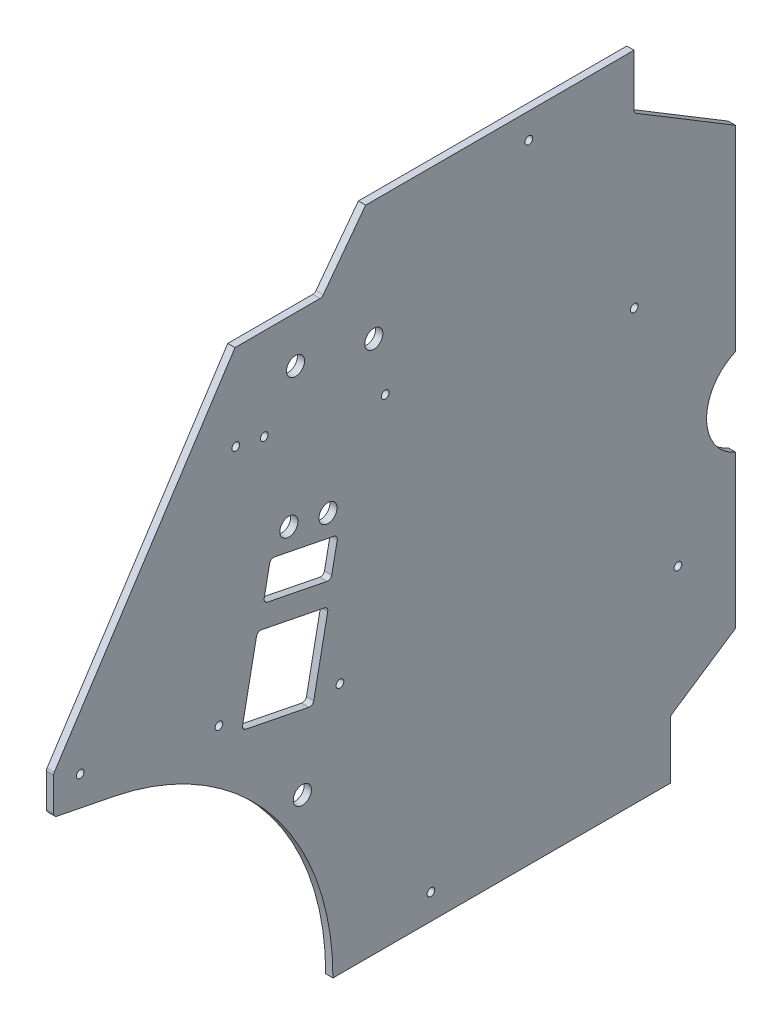
SolidWorks part; units mm, degrees
note: The reader was unsure of these and kept them because the rebuilt part matched: thickness of "Base-Flange1", "Sheet-Metal1", "Sheet-Metal3", "Sheet-Metal4", "Sheet-Metal5", "Sheet-Metal6", "Sheet-Metal7", "Sheet-Metal8", "Sheet-Metal9", "Sheet-Metal10", "Sheet-Metal11", "Sheet-Metal12", "Sheet-Metal13".
material "PE High Density"
ref_plane "Front Plane" through (0, 0, 0) normal (0, 0, 1) x (1, 0, 0)
ref_plane "Top Plane" through (0, 0, 0) normal (0, 1, 0) x (1, 0, 0)
ref_plane "Right Plane" through (0, 0, 0) normal (1, 0, 0) x (0, 0, -1)
sketch "Sketch1" plane through (0, 0, 0) normal (1, 0, 0) x (0, 0, -1)
  line L0 (0, 38.1) -> (-1054.1, 247.7735) construction
  line L1 (-812.8, 571.5) -> (-812.8, 527.05) construction
  line L2 (-381, 0) -> (-425.45, 0) construction
  line L3 (-381, 0) -> (-381, 527.05) construction
  line L4 (-381, 527.05) -> (-425.45, 527.05) construction
  line L5 (-425.45, 0) -> (-425.45, 527.05) construction
  line L6 (0, 571.5) -> (-857.25, 571.5) construction
  line L7 (0, 571.5) -> (0, 527.05) construction
  line L8 (0, 527.05) -> (-857.25, 527.05) construction
  line L9 (-857.25, 571.5) -> (-857.25, 527.05) construction
  line L10 (-1054.1, 247.7735) -> (-876.3, 520.7)
  line L12 (-438.15, 125.2535) -> (-438.15, 571.5)
  line L13 (-438.15, 571.5) -> (-800.1, 571.5)
  line L14 (-800.1, 571.5) -> (-800.1, 520.7)
  line L15 (-800.1, 520.7) -> (-876.3, 520.7)
  line L16 (-74.137, 298.8741) -> (-1150.5711, 512.9902) construction
  line L18 (-790.575, 0) -> (-438.15, 0)
  line L19 (-438.15, 0) -> (-438.15, 125.2535)
  line L20 (-1054.1, 247.7735) -> (-982.1765, 233.467)
  arc A0 (-982.1765, 233.467) -> (-790.575, 0) centre (-1028.6159, 0) cw
  dimension "D1" = 38.1
  dimension "D2" = 381
  dimension "D3" = 44.45
  dimension "D4" = 11.25
  dimension "D5" = 628.65
  dimension "D6" = 571.5
  dimension "D7" = 44.45
  dimension "D8" = 812.8
  dimension "D9" = 12.7
  dimension "D10" = 241.3
  dimension "D11" = 12.7
  dimension "D12" = 12.7
  dimension "D13" = 33.083
  dimension "D14" = 352.425
  dimension "D15" = 76.2
base flange "Base-Flange1" sketch "Sketch1" thickness 6.35 reverse thickness direction no parameters "D1"=3
hole_wizard "1/4 Clearance Hole1" positions "Sketch9" profile "Sketch10" hole size "1/4" standard "ANSI Inch" end condition through all
sketch "Sketch9" plane through (0, 0, 0) normal (1, 0, 0) x (0, 0, -1)
  line L0 (-1049.1447, 272.6855) -> (-451.258, 153.7584) construction
  line L1 (-1054.1, 247.7735) -> (-456.2133, 128.8465) construction
  line L2 (0, 38.1) -> (-1054.1, 247.7735) construction
  line L3 (-1054.1, 247.7735) -> (-1049.1447, 272.6855) construction
  line L4 (-750.2014, 213.2219) -> (-755.1566, 188.31) construction
  line L5 (-438.15, 384.2296) -> (-920.4692, 480.1689) construction
  line L8 (-438.15, 0) -> (-438.15, 571.5) construction
  line L9 (-477.0095, 366.0616) -> (-925.4245, 455.2569) construction
  line L10 (-925.4245, 455.2569) -> (-920.4692, 480.1689) construction
  line L11 (-701.217, 410.6593) -> (-696.2617, 435.5712) construction
  line L12 (-890.331, 241.0955) -> (-784.4553, 220.0355) construction
  line L13 (-890.331, 241.0955) -> (-850.6887, 440.391) construction
  line L14 (-784.4553, 220.0355) -> (-744.8129, 419.331) construction
  line L15 (-850.6887, 440.391) -> (-744.8129, 419.331) construction
  line L16 (-1054.1, 370.7872) -> (-456.2133, 251.8601) construction
  line L17 (-800.1, 527.05) -> (-438.15, 527.05) construction
  line L18 (-800.1, 571.5) -> (-800.1, 520.7) construction
  line L19 (-438.15, 0) -> (-438.15, 571.5) construction
  line L20 (-438.15, 571.5) -> (-800.1, 571.5) construction
  line L21 (-619.125, 527.05) -> (-619.125, 571.5) construction
  line L22 (-438.15, 44.45) -> (-794.762, 44.45) construction
  line L23 (-790.575, 0) -> (-438.15, 0) construction
  line L24 (-704.85, 44.45) -> (-704.85, 0) construction
  circle A0 centre (-1054.1, 370.7872) radius 120.65 construction
  arc A1 (-790.575, 0) -> (-982.1765, 233.467) centre (-1028.6159, 0) ccw construction
  point P18 (-1011.7768, 265.2525)
  point P39 (-488.6259, 161.1914)
  point P60 (-875.6006, 445.3463)
  point P71 (-526.8334, 375.9722)
  point P123 (-850.6887, 440.391)
  point P126 (-744.8129, 419.331)
  point P129 (-890.331, 241.0955)
  point P132 (-784.4553, 220.0355)
  point P139 (-619.125, 549.275)
  point P166 (-704.85, 22.225)
  dimension "D12" = 241.3
  dimension "D1" = 25.4
  dimension "D2" = 38.1
  dimension "D4" = 609.6
  dimension "D5" = 254
  dimension "D6" = 25.4
  dimension "D7" = 50.8
  dimension "D8" = 44.45
  dimension "D9" = 457.2
  dimension "D10" = 107.95
  dimension "D11" = 203.2
  dimension "D13" = 76.2
  dimension "D14" = 85.725
  dimension "D16" = 44.45
  dimension "D17" = 266.7
sketch "Sketch10" plane through (0, 22.225, 704.85) normal (0, 1, 0) x (0, 0, -1)
  line L0 (0, 0) -> (0, 6.35)
  line L1 (0, 6.35) -> (3.3782, 6.35)
  line L2 (3.3782, 6.35) -> (3.3782, 0)
  line L5 (3.3782, 0) -> (0, 0)
  line L11 (0, -6.35) -> (0, 107.95) construction
  dimension "Thru Hole Dia." = 6.7564
  dimension "Thru Hole Depth" = 6.35
sketch "Sketch11" plane through (0, 0, 0) normal (1, 0, 0) x (0, 0, -1)
  line L0 (-845.2967, 345.4396) -> (-786.1308, 333.6708)
  line L1 (-845.2967, 345.4396) -> (-851.4908, 314.2997)
  line L2 (-786.1308, 333.6708) -> (-792.3249, 302.5309)
  line L3 (-851.4908, 314.2997) -> (-792.3249, 302.5309)
  line L4 (-1054.1, 370.7872) -> (-456.2133, 251.8601) construction
  line L5 (-871.7487, 334.5153) -> (-765.8729, 313.4553) construction
  line L6 (-890.331, 241.0955) -> (-850.6887, 440.391) construction
  line L7 (-784.4553, 220.0355) -> (-744.8129, 419.331) construction
  line L8 (-848.3937, 329.8697) -> (-789.2279, 318.1009) construction
  point P0 (-848.3937, 329.8697)
  point P3 (-818.8108, 323.9853)
  dimension "D1" = 31.75
  dimension "D2" = 60.325
extrude "Cut-Extrude1" cut sketch "Sketch11" against normal through all normal cut yes
hole_wizard "27/32 (0.84375) Diameter Hole1" positions "Sketch12" profile "Sketch13" hole size "27/32" standard "ANSI Inch" end condition through all
sketch "Sketch12" plane through (0, 0, 0) normal (1, 0, 0) x (0, 0, -1)
  line L0 (-837.3932, 230.5655) -> (-797.7508, 429.861) construction
  line L1 (-890.331, 241.0955) -> (-784.4553, 220.0355) construction
  line L2 (-850.6887, 440.391) -> (-744.8129, 419.331) construction
  line L3 (-822.4528, 234.068) -> (-849.8559, 239.5189) construction
  line L4 (-1049.1447, 272.6855) -> (-451.258, 153.7584) construction
  line L5 (-1054.1, 370.7872) -> (-456.2133, 251.8601) construction
  point P0 (-849.8559, 239.5189)
  point P2 (-822.4528, 234.068)
  dimension "D1" = 13.97
  dimension "D2" = 88.9
sketch "Sketch13" plane through (0, 239.5189, 849.8559) normal (0, 1, 0) x (0, 0, -1)
  line L0 (0, 0) -> (0, 6.35)
  line L1 (0, 6.35) -> (10.7156, 6.35)
  line L2 (10.7156, 6.35) -> (10.7156, 0)
  line L5 (10.7156, 0) -> (0, 0)
  line L11 (0, -6.35) -> (0, 107.95) construction
  dimension "Thru Hole Dia." = 21.4312
  dimension "Thru Hole Depth" = 6.35
sketch "Sketch14" plane through (0, 0, 0) normal (1, 0, 0) x (0, 0, -1)
  line L0 (-864.1972, 258.5575) -> (-801.9173, 246.1693) construction
  line L1 (-864.1972, 258.5575) -> (-870.3913, 227.4176)
  line L2 (-801.9173, 246.1693) -> (-808.1115, 215.0294)
  line L3 (-870.3913, 227.4176) -> (-808.1115, 215.0294)
  line L4 (-864.1972, 258.5575) -> (-856.7643, 295.9255)
  line L5 (-851.4908, 314.2997) -> (-792.3249, 302.5309) construction
  line L6 (-849.8559, 239.5189) -> (-822.4528, 234.068) construction
  line L7 (-836.1543, 236.7935) -> (-833.0573, 252.3634) construction
  line L8 (-856.7643, 295.9255) -> (-794.4844, 283.5372)
  line L9 (-794.4844, 283.5372) -> (-801.9173, 246.1693)
  circle A0 centre (-849.8559, 239.5189) radius 10.7156 construction
  circle A1 centre (-849.8559, 239.5189) radius 10.7156 construction
  dimension "D1" = 15.875
  dimension "D2" = 31.75
  dimension "D3" = 63.5
  dimension "D4" = 19.05
  dimension "D5" = 38.1
extrude "Cut-Extrude2" cut sketch "Sketch14" against normal through all normal cut yes
sketch "Sketch15" plane through (0, 0, 0) normal (1, 0, 0) x (0, 0, -1)
  line L0 (-438.15, 0) -> (-438.15, 571.5) construction
  line L1 (-438.15, 571.5) -> (-476.25, 571.5)
  line L2 (-438.15, 571.5) -> (-438.15, 501.878)
  line L3 (-438.15, 501.878) -> (-476.25, 523.875)
  line L4 (-476.25, 571.5) -> (-476.25, 523.875)
  line L5 (-438.15, 0) -> (-495.3, 0)
  line L6 (-438.15, 0) -> (-438.15, 88.9)
  line L7 (-438.15, 88.9) -> (-495.3, 50.8)
  line L8 (-495.3, 0) -> (-495.3, 50.8)
  line L9 (-438.15, 571.5) -> (-800.1, 571.5) construction
  dimension "D1" = 60
  dimension "D2" = 38.1
  dimension "D3" = 47.625
  dimension "D4" = 57.15
  dimension "D5" = 50.8
  dimension "D6" = 88.9
extrude "Cut-Extrude3" cut sketch "Sketch15" against normal through all normal cut yes
sketch "Sketch16" plane through (-6.35, 0, 0) normal (-1, 0, 0) x (0, 0, 1)
  line L0 (795.5084, 300.5226) -> (797.4905, 290.5578) construction
  line L1 (851.4908, 314.2997) -> (792.3249, 302.5309) construction
  line L4 (815.7138, 339.5552) -> (821.9079, 308.4153) construction
  line L5 (786.1308, 333.6708) -> (845.2967, 345.4396) construction
  line L6 (798.7398, 303.8069) -> (801.2273, 291.3011)
  line L9 (793.7537, 289.8145) -> (791.7716, 299.7793)
  line L10 (791.7716, 299.7793) -> (791.1522, 302.8933)
  line L12 (791.1522, 302.8933) -> (791.7055, 305.6449)
  line L13 (792.3249, 302.5309) -> (786.1308, 333.6708) construction
  line L14 (791.7055, 305.6449) -> (792.3249, 302.5309)
  line L15 (792.3249, 302.5309) -> (798.7398, 303.8069)
  line L16 (851.4908, 314.2997) -> (845.076, 313.0237)
  line L17 (850.8714, 317.4137) -> (851.4908, 314.2997)
  line L18 (852.4356, 315.0833) -> (850.8714, 317.4137)
  line L19 (853.055, 311.9693) -> (852.4356, 315.0833)
  line L20 (855.0371, 302.0045) -> (853.055, 311.9693)
  line L21 (845.076, 313.0237) -> (847.5635, 300.5179)
  circle A4 centre (795.5084, 300.5226) radius 3.81 construction
  circle A5 centre (797.4905, 290.5578) radius 3.81 construction
  circle A6 centre (851.3003, 301.2612) radius 3.81 construction
  circle A7 centre (849.3182, 311.226) radius 3.81 construction
  arc A8 (793.7537, 289.8145) -> (801.2273, 291.3011) centre (797.4905, 290.5578) ccw
  arc A9 (855.0371, 302.0045) -> (847.5635, 300.5179) centre (851.3003, 301.2612) cw
  dimension "D4" = 7.62
  dimension "D1" = 2.5908
  dimension "D2" = 10.16
  dimension "D3" = 54.864
  dimension "D5" = 3.175
  dimension "D6" = 3.175
extrude "Cut-Extrude4" [suppressed] cut sketch "Sketch16" against normal through all
fillet "Fillet1" [suppressed] radius 3.556
sketch "Sketch17" plane through (-6.35, 0, 0) normal (-1, 0, 0) x (0, 0, 1)
  line L0 (1035.05, 277.0156) -> (1035.05, 243.9842)
  line L1 (876.3, 520.7) -> (1054.1, 247.7735) construction
  line L2 (1054.1, 247.7735) -> (982.1765, 233.467) construction
  line L3 (1035.05, 243.9842) -> (1054.1, 247.7735)
  line L4 (1054.1, 247.7735) -> (1035.05, 277.0156)
  dimension "D1" = 19.05
extrude "Cut-Extrude5" cut sketch "Sketch17" against normal through all normal cut yes
sketch "Sketch18" plane through (-6.35, 0, 0) normal (-1, 0, 0) x (0, 0, 1)
  line L0 (476.25, 523.875) -> (438.15, 501.878)
  line L1 (476.25, 571.5) -> (527.05, 571.5)
  line L2 (476.25, 571.5) -> (476.25, 523.875)
  line L4 (527.05, 571.5) -> (527.05, 523.875)
  line L5 (438.15, 501.878) -> (438.15, 470.128)
  line L6 (438.15, 88.9) -> (438.15, 501.878) construction
  line L7 (438.15, 470.128) -> (527.05, 523.875)
  dimension "D1" = 50.8
  dimension "D2" = 31.75
extrude "Cut-Extrude6" cut sketch "Sketch18" against normal through all normal cut yes
sketch "Sketch20" plane through (-6.35, 0, 0) normal (-1, 0, 0) x (0, 0, 1)
  line L0 (438.15, 88.9) -> (438.15, 470.128) construction
  line L1 (1035.05, 243.9842) -> (438.15, 243.9842) construction
  line L2 (1035.05, 277.0156) -> (438.15, 277.0156) construction
  line L3 (438.15, 277.0156) -> (438.15, 243.9842) construction
  line L4 (438.15, 298.5999) -> (438.15, 222.3999)
  arc A0 (438.15, 298.5999) -> (438.15, 222.3999) centre (422.275, 260.4999) cw
  point P11 (438.15, 260.4999)
  point P14 (463.55, 260.4999)
  dimension "D1" = 25.4
  dimension "D2" = 76.2
extrude "Cut-Extrude7" cut sketch "Sketch20" against normal through all normal cut yes
sketch "Sketch22" plane through (-6.35, 0, 0) normal (-1, 0, 0) x (0, 0, 1)
  line L0 (800.1, 520.7) -> (762, 571.5)
  line L1 (527.05, 571.5) -> (800.1, 571.5) construction
  line L2 (762, 571.5) -> (800.1, 571.5)
  line L3 (800.1, 571.5) -> (800.1, 520.7)
  dimension "D1" = 38.1
extrude "Cut-Extrude8" cut sketch "Sketch22" against normal through all normal cut yes
sketch "Sketch23" plane through (0, 0, 0) normal (1, 0, 0) x (0, 0, -1)
  line L0 (-754.8251, 466.6434) -> (-817.3857, 152.1301) construction
  line L1 (-754.8251, 466.6434) -> (-823.333, 480.2705) construction
  line L2 (-817.3857, 152.1301) -> (-885.8936, 165.7572) construction
  line L3 (-823.333, 480.2705) -> (-885.8936, 165.7572) construction
  line L4 (-754.8251, 466.6434) -> (-885.8936, 165.7572) construction
  line L5 (-817.3857, 152.1301) -> (-823.333, 480.2705) construction
  line L6 (-870.3913, 227.4176) -> (-808.1115, 215.0294) construction
  line L7 (-789.2279, 318.1009) -> (-848.3937, 329.8697) construction
  line L10 (-815.7138, 339.5552) -> (-821.9079, 308.4153) construction
  line L11 (-786.1308, 333.6708) -> (-845.2967, 345.4396) construction
  line L12 (-851.4908, 314.2997) -> (-792.3249, 302.5309) construction
  line L13 (-792.3249, 302.5309) -> (-786.1308, 333.6708) construction
  line L14 (-845.2967, 345.4396) -> (-851.4908, 314.2997) construction
  line L16 (-885.8936, 172.173) -> (-891.4498, 168.9651) construction
  line L17 (-891.4498, 168.9651) -> (-891.4498, 162.5493) construction
  line L18 (-891.4498, 162.5493) -> (-885.8936, 159.3414) construction
  line L19 (-885.8936, 159.3414) -> (-880.3373, 162.5493) construction
  line L20 (-880.3373, 162.5493) -> (-880.3373, 168.9651) construction
  line L21 (-880.3373, 168.9651) -> (-885.8936, 172.173) construction
  circle A0 centre (-885.8936, 165.7572) radius 5.5562 construction
  circle A1 centre (-885.8936, 165.7572) radius 6.4158 construction
  circle A2 centre (-885.8936, 165.7572) radius 7.9375
  point P1 (-820.3593, 316.2003)
  dimension "D6" = 15.875
  dimension "D1" = 69.85
  dimension "D2" = 320.675
  dimension "D3" = 7.9375
  dimension "D4" = 11.1125
  dimension "D5" = 1.5217
hole_wizard "5/8 (0.625) Diameter Hole1" positions "Sketch24" profile "Sketch25" hole size "5/8" standard "ANSI Inch" end condition through all
sketch "Sketch24" plane through (0, 0, 0) normal (1, 0, 0) x (0, 0, -1)
  line L0 (-786.1308, 333.6708) -> (-845.2967, 345.4396) construction
  line L1 (-829.173, 361.4008) -> (-794.9191, 354.5872) construction
  line L2 (-815.7138, 339.5552) -> (-812.0461, 357.994) construction
  line L3 (-845.9649, 342.0805) -> (-786.799, 330.3116) construction
  line L4 (-845.9649, 342.0805) -> (-850.8226, 317.6589) construction
  line L5 (-786.799, 330.3116) -> (-791.6567, 305.8901) construction
  line L6 (-850.8226, 317.6589) -> (-791.6567, 305.8901) construction
  line L7 (-789.2279, 318.1009) -> (-848.3937, 329.8697) construction
  line L8 (-792.3249, 302.5309) -> (-786.1308, 333.6708) construction
  line L9 (-845.2967, 345.4396) -> (-851.4908, 314.2997) construction
  line L10 (-816.3819, 336.196) -> (-812.0461, 357.994) construction
  point P0 (-823.333, 480.2705)
  point P3 (-754.8251, 466.6434)
  point P6 (-817.3857, 152.1301)
  point P14 (-829.173, 361.4008)
  point P17 (-794.9191, 354.5872)
  dimension "D2" = 34.925
  dimension "D3" = 24.9
  dimension "D4" = 22.225
sketch "Sketch25" plane through (0, 480.2705, 823.333) normal (0, 1, 0) x (0, 0, -1)
  line L0 (0, 0) -> (0, 6.35)
  line L1 (0, 6.35) -> (7.9375, 6.35)
  line L2 (7.9375, 6.35) -> (7.9375, 0)
  line L5 (7.9375, 0) -> (0, 0)
  line L11 (0, -6.35) -> (0, 107.95) construction
  dimension "Thru Hole Dia." = 15.875
  dimension "Thru Hole Depth" = 6.35
fillet "Fillet2" radius 3.556 13 edges at (-3.175, 50.8, 495.3) (-3.175, 227.4176, 870.3913) (-3.175, 215.0294, 808.1115) (-3.175, 333.6708, 786.1308) (-3.175, 345.4396, 845.2967) (-3.175, 314.2997, 851.4908) (-3.175, 302.5309, 792.3249) (-3.175, 277.0156, 1035.05) (-3.175, 243.9842, 1035.05) (-3.175, 523.875, 527.05) (-3.175, 520.7, 800.1) (-3.175, 283.5372, 794.4844) (-3.175, 295.9255, 856.7643)
sketch "Bend-Lines1" [suppressed] plane through (0, 0, 0) normal (0, 1, 0) x (1, 0, 0)
sketch "Bounding-Box1" [suppressed] plane through (0, 0, 0) normal (0, 1, 0) x (1, 0, 0)
sheet metal parameters "Sheet-Metal1" thickness 6.35 parameters "D1"=3, "D7"=2.3622
flat pattern "Flat-Pattern1" [suppressed]
sketch "Bend-Lines2" plane through (0, 0, 0) normal (0, 1, 0) x (1, 0, 0)
sketch3d "Bounding-Box2" [suppressed]
  line L0 (602.2996, 0, 0) -> (-13.6504, 0, 0) construction
  line L1 (602.2996, 571.5, 0) -> (-13.6504, 571.5, 0) construction
  line L2 (602.2996, 0, 0) -> (602.2996, 571.5, 0) construction
  line L3 (-13.6504, 0, 0) -> (-13.6504, 571.5, 0) construction
sheet metal parameters "Sheet-Metal3" thickness 6.35 parameters "D1"=3, "D7"=2.3622
flat pattern "Flat-Pattern1"
sketch "Bend-Lines2" plane through (0, 0, 0) normal (1, 0, 0) x (0, 0, -1)
  line L0 (-438.15, 571.7838) -> (-800.1, 571.7838) construction
  line L1 (-438.15, 571.7838) -> (-800.1, 571.7838) construction
sketch3d "Bounding-Box2" [suppressed]
  line L0 (602.2996, 0, 0) -> (-13.6504, 0, 0) construction
  line L1 (602.2996, 614.1555, 0) -> (-13.6504, 614.1555, 0) construction
  line L2 (602.2996, 0, 0) -> (602.2996, 614.1555, 0) construction
  line L3 (-13.6504, 0, 0) -> (-13.6504, 614.1555, 0) construction
sheet metal parameters "Sheet-Metal4" thickness 6.35 parameters "D1"=3, "D7"=2.3622
flat pattern "Flat-Pattern1"
sketch "Bend-Lines2" plane through (0, 0, 0) normal (1, 0, 0) x (0, 0, -1)
  line L0 (-438.15, 571.7838) -> (-800.1, 571.7838) construction
  line L1 (-438.15, 571.7838) -> (-800.1, 571.7838) construction
sketch3d "Bounding-Box2" [suppressed]
  line L0 (602.2996, 0, 0) -> (-13.6504, 0, 0) construction
  line L1 (602.2996, 614.1555, 0) -> (-13.6504, 614.1555, 0) construction
  line L2 (602.2996, 0, 0) -> (602.2996, 614.1555, 0) construction
  line L3 (-13.6504, 0, 0) -> (-13.6504, 614.1555, 0) construction
sheet metal parameters "Sheet-Metal5" thickness 6.35 parameters "D1"=3, "D7"=2.3622
flat pattern "Flat-Pattern1"
sketch "Bend-Lines2" plane through (0, 0, 0) normal (1, 0, 0) x (0, 0, -1)
sketch3d "Bounding-Box2" [suppressed]
  line L0 (602.2996, 0, 0) -> (-13.6504, 0, 0) construction
  line L1 (602.2996, 571.5, 0) -> (-13.6504, 571.5, 0) construction
  line L2 (602.2996, 0, 0) -> (602.2996, 571.5, 0) construction
  line L3 (-13.6504, 0, 0) -> (-13.6504, 571.5, 0) construction
sheet metal parameters "Sheet-Metal6" thickness 6.35 parameters "D1"=3, "D7"=2.3622
flat pattern "Flat-Pattern1"
sketch "Bend-Lines2" plane through (0, 0, 0) normal (1, 0, 0) x (0, 0, -1)
sketch3d "Bounding-Box2" [suppressed]
  line L0 (602.2996, 0, 0) -> (-13.6504, 0, 0) construction
  line L1 (602.2996, 571.5, 0) -> (-13.6504, 571.5, 0) construction
  line L2 (602.2996, 0, 0) -> (602.2996, 571.5, 0) construction
  line L3 (-13.6504, 0, 0) -> (-13.6504, 571.5, 0) construction
sheet metal parameters "Sheet-Metal7" thickness 6.35 parameters "D1"=3, "D7"=2.3622
flat pattern "Flat-Pattern1"
sketch "Bend-Lines2" plane through (0, 0, 0) normal (1, 0, 0) x (0, 0, -1)
sketch3d "Bounding-Box2" [suppressed]
  line L0 (602.2996, 0, 0) -> (-13.6504, 0, 0) construction
  line L1 (602.2996, 571.5, 0) -> (-13.6504, 571.5, 0) construction
  line L2 (602.2996, 0, 0) -> (602.2996, 571.5, 0) construction
  line L3 (-13.6504, 0, 0) -> (-13.6504, 571.5, 0) construction
sheet metal parameters "Sheet-Metal8" thickness 6.35 parameters "D1"=3, "D7"=2.3622
flat pattern "Flat-Pattern1"
sketch "Bend-Lines2" plane through (0, 0, 0) normal (1, 0, 0) x (0, 0, -1)
sketch3d "Bounding-Box2" [suppressed]
  line L0 (602.2996, 0, 0) -> (-11.6455, 0, 0) construction
  line L1 (602.2996, 571.5, 0) -> (-11.6455, 571.5, 0) construction
  line L2 (602.2996, 0, 0) -> (602.2996, 571.5, 0) construction
  line L3 (-11.6455, 0, 0) -> (-11.6455, 571.5, 0) construction
sheet metal parameters "Sheet-Metal9" thickness 6.35 parameters "D1"=3, "D7"=2.3622
flat pattern "Flat-Pattern1"
sketch "Bend-Lines2" plane through (0, 0, 0) normal (1, 0, 0) x (0, 0, -1)
sketch3d "Bounding-Box2" [suppressed]
  line L0 (602.2996, 0, 0) -> (5.3996, 0, 0) construction
  line L1 (602.2996, 571.5, 0) -> (5.3996, 571.5, 0) construction
  line L2 (602.2996, 0, 0) -> (602.2996, 571.5, 0) construction
  line L3 (5.3996, 0, 0) -> (5.3996, 571.5, 0) construction
sheet metal parameters "Sheet-Metal10" thickness 6.35 parameters "D1"=3, "D7"=2.3622
flat pattern "Flat-Pattern1"
sketch "Bend-Lines2" plane through (0, 0, 0) normal (1, 0, 0) x (0, 0, -1)
sketch3d "Bounding-Box2" [suppressed]
  line L0 (602.2996, 0, 0) -> (5.3996, 0, 0) construction
  line L1 (602.2996, 571.5, 0) -> (5.3996, 571.5, 0) construction
  line L2 (602.2996, 0, 0) -> (602.2996, 571.5, 0) construction
  line L3 (5.3996, 0, 0) -> (5.3996, 571.5, 0) construction
sheet metal parameters "Sheet-Metal11" thickness 6.35 parameters "D1"=3, "D7"=2.3622
flat pattern "Flat-Pattern1"
sketch "Bend-Lines2" plane through (0, 0, 0) normal (1, 0, 0) x (0, 0, -1)
sketch3d "Bounding-Box2" [suppressed]
  line L0 (602.2996, 0, 0) -> (5.3996, 0, 0) construction
  line L1 (602.2996, 571.5, 0) -> (5.3996, 571.5, 0) construction
  line L2 (602.2996, 0, 0) -> (602.2996, 571.5, 0) construction
  line L3 (5.3996, 0, 0) -> (5.3996, 571.5, 0) construction
sheet metal parameters "Sheet-Metal12" thickness 6.35 parameters "D1"=3, "D7"=2.3622
flat pattern "Flat-Pattern1"
sketch "Bend-Lines2" plane through (0, 0, 0) normal (1, 0, 0) x (0, 0, -1)
sketch3d "Bounding-Box2" [suppressed]
  line L0 (602.2996, 0, 0) -> (5.3996, 0, 0) construction
  line L1 (602.2996, 571.5, 0) -> (5.3996, 571.5, 0) construction
  line L2 (602.2996, 0, 0) -> (602.2996, 571.5, 0) construction
  line L3 (5.3996, 0, 0) -> (5.3996, 571.5, 0) construction
sheet metal parameters "Sheet-Metal13" thickness 6.35 parameters "D1"=3, "D7"=2.3622
flat pattern "Flat-Pattern1"
sketch "Bend-Lines2" plane through (0, 0, 0) normal (1, 0, 0) x (0, 0, -1)
sketch3d "Bounding-Box2" [suppressed]
  line L0 (590.4653, 571.5005, 0) -> (-6.4345, 571.4996, 0) construction
  line L1 (590.4661, 0.0005, 0) -> (-6.4337, -0.0003, 0) construction
  line L2 (590.4653, 571.5005, 0) -> (590.4661, 0.0005, 0) construction
  line L3 (-6.4345, 571.4996, 0) -> (-6.4337, -0.0003, 0) construction
equation "\"D3@Sketch24\"=24.9/25.4"
